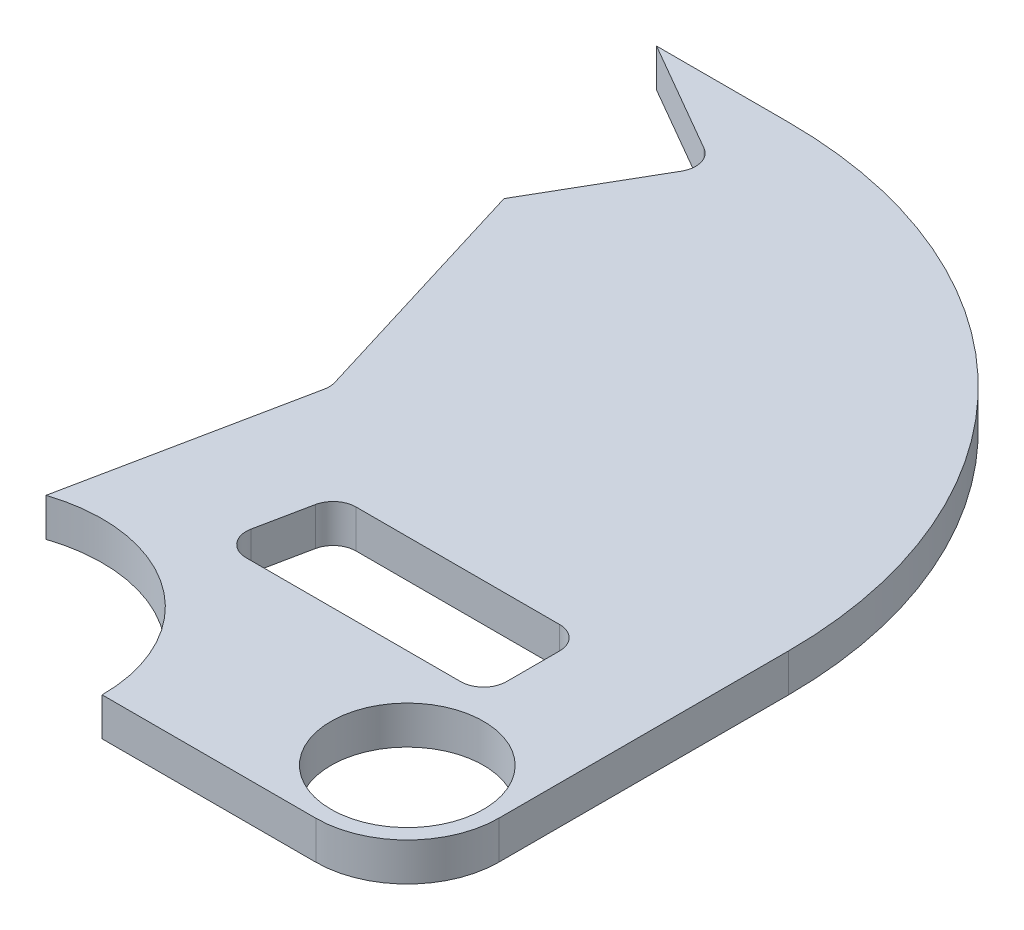
SolidWorks part; units mm, degrees
ref_plane "Front Plane" through (0, 0, 0) normal (0, 0, 1) x (1, 0, 0)
ref_plane "Top Plane" through (0, 0, 0) normal (0, 1, 0) x (1, 0, 0)
ref_plane "Right Plane" through (0, 0, 0) normal (1, 0, 0) x (0, 0, -1)
sketch "Profile Sketch" plane through (0, 0, 0) normal (0, 1, 0) x (1, 0, 0)
  line L0 (0, 60) -> (0, 0) construction
  line L1 (0, 0) -> (60, 0) construction
  line L2 (0, 60) -> (-17.3205, 60)
  line L3 (-17.3205, 60) -> (0, 50)
  line L4 (0, 50) -> (-10, 32.6795)
  line L5 (-10, 32.6795) -> (0, 0)
  line L6 (60, 0) -> (60, -38)
  line L7 (0, 0) -> (-6.3339, -31.0294)
  line L8 (-6.3339, -31.0294) -> (-9.798, -48) construction
  line L9 (48, -50) -> (20, -50)
  line L10 (12.8538, -12.0294) -> (45, -12.0294)
  line L11 (45, -12.0294) -> (45, -25)
  line L12 (45, -25) -> (10.2062, -25)
  line L13 (10.2062, -25) -> (12.8538, -12.0294)
  line L14 (11.53, -18.5147) -> (-3.1669, -15.5147) construction
  line L15 (45, -18.5147) -> (60, -18.5147) construction
  line L16 (28.9269, -12.0294) -> (28.9269, 0) construction
  line L17 (48, -38) -> (60, -38) construction
  line L18 (48, -38) -> (48, -50) construction
  arc A0 (60, 0) -> (0, 60) centre (0, 0) ccw
  arc A1 (20, -50) -> (-6.3339, -31.0294) centre (0, -50) ccw
  circle A2 centre (48, -38) radius 10
  circle A3 centre (0, -50) radius 10 construction
  circle A4 centre (0, -50) radius 20 construction
  arc A6 (48, -50) -> (60, -38) centre (48, -38) ccw
  point P28 (0, 0)
  point P30 (28.9269, -12.0294)
  point P31 (0, 0)
  point P33 (60, -50)
  dimension "D1" = 30
  dimension "D2" = 40
  dimension "D3" = 20
  dimension "D6" = 60
  dimension "D11" = 25
  dimension "D4" = 12
  dimension "D5" = 12
  dimension "D7" = 10
  dimension "D8" = 10
  dimension "D9" = 50
  dimension "D10" = 15
extrude "Profile Extrude" add sketch "Profile Sketch" along normal blind 5
fillet "Trapezoid Fillet" radius 3 4 edges at (45, 2.5, 12.0294) (45, 2.5, 25) (10.2062, 2.5, 25) (12.8538, 2.5, 12.0294)
fillet "Claw Fillet" radius 3 2 edges at (0, 2.5, 0) (0, 2.5, -50)
